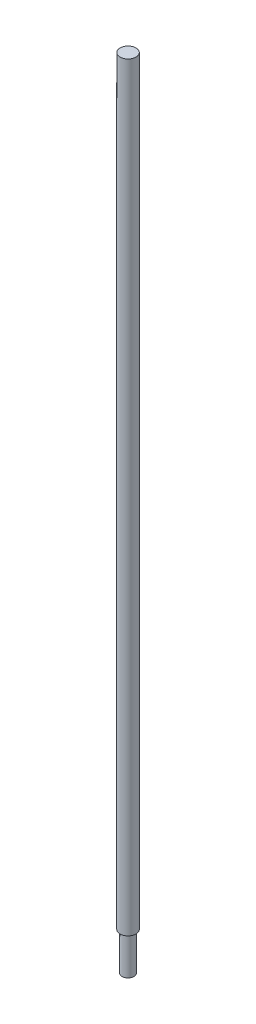
SolidWorks part; units mm, degrees
ref_plane "Ebene vorne" through (0, 0, 0) normal (0, 0, 1) x (1, 0, 0)
ref_plane "Ebene oben" through (0, 0, 0) normal (0, 1, 0) x (1, 0, 0)
ref_plane "Ebene rechts" through (0, 0, 0) normal (1, 0, 0) x (0, 0, -1)
sketch "Position" plane through (0, 0, 0) normal (0, 1, 0) x (1, 0, 0)
  circle A0 centre (14, 0) radius 1.5
  circle A1 centre (0, 0) radius 4.5
sketch "Length" plane through (0, 0, 0) normal (0, 0, 1) x (1, 0, 0)
  line L0 (0, 218) -> (0, 618)
  line L4 (14, 237) -> (14, 618)
  point P7 (0, 210.9748)
  point P9 (0, 217.541)
sketch "Skizze3" plane through (0, 0, 0) normal (0, 1, 0) x (1, 0, 0)
  line L0 (-23.35, 0) -> (23.35, 0) construction
  circle A0 centre (0, 0) radius 4
extrude "Aufsatz-Linear austragen1" add sketch "Skizze3" along normal up to vertex (618 mm away) from vertex up to point (0, 618, 0) starting at point (0, 218, 0)
sketch "Skizze5" plane through (0, 218, 0) normal (0, -1, 0) x (1, 0, 0)
  circle A0 centre (0, 0) radius 4
  circle A1 centre (0, 0) radius 3
extrude "Schnitt-Linear austragen1" cut sketch "Skizze5" against normal up to vertex (19 mm away) up to point (14, 237, 0)
